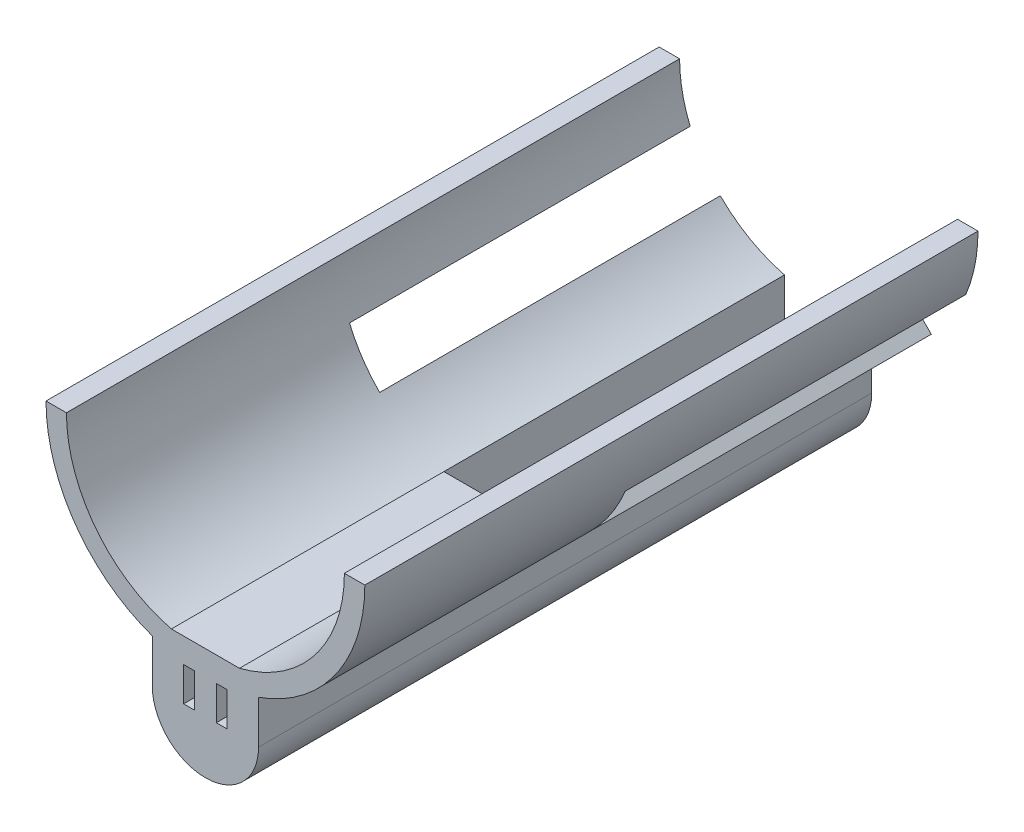
SolidWorks part; units mm, degrees
ref_plane "Front Plane" through (0, 0, 0) normal (0, 0, 1) x (1, 0, 0)
ref_plane "Top Plane" through (0, 0, 0) normal (0, 1, 0) x (1, 0, 0)
ref_plane "Right Plane" through (0, 0, 0) normal (1, 0, 0) x (0, 0, -1)
sketch "Sketch1" plane through (0, 0, 0) normal (0, 0, 1) x (1, 0, 0)
  line L0 (0, 20.4) -> (0, 23.4)
  line L1 (7.8067, 18.8471) -> (8.9548, 21.6188)
  line L2 (14.425, 14.425) -> (16.5463, 16.5463)
  line L3 (18.8471, 7.8067) -> (21.6188, 8.9548)
  line L4 (20.4, 0) -> (23.4, 0)
  line L5 (18.8471, -7.8067) -> (21.6188, -8.9548) [skipped]
  line L6 (14.425, -14.425) -> (16.5463, -16.5463) [skipped]
  line L7 (7.8067, -18.8471) -> (8.9548, -21.6188) [skipped]
  line L8 (0, -20.4) -> (0, -23.4) [skipped]
  line L9 (-7.8067, -18.8471) -> (-8.9548, -21.6188) [skipped]
  line L10 (-14.425, -14.425) -> (-16.5463, -16.5463) [skipped]
  line L11 (-18.8471, -7.8067) -> (-21.6188, -8.9548) [skipped]
  line L12 (-20.4, 0) -> (-23.4, 0)
  line L13 (-18.8471, 7.8067) -> (-21.6188, 8.9548)
  line L14 (-14.425, 14.425) -> (-16.5463, 16.5463)
  line L15 (-7.8067, 18.8471) -> (-8.9548, 21.6188)
  line L16 (-7.8, -28.4) -> (-7.8, -22.0617)
  line L18 (-5, -28.4) -> (-5, -19.7778)
  line L19 (5, -28.4) -> (5, -19.7778)
  line L21 (7.8, -28.4) -> (7.8, -22.0617)
  line L22 (-7.8, -36.2) -> (-7.8, -22.8596) construction
  line L23 (7.8, -36.2) -> (7.8, -22.8596) construction
  line L24 (-5, -33.4) -> (5, -33.4) construction
  line L25 (-5, -33.4) -> (-5, -22.8596) construction
  line L26 (5, -33.4) -> (5, -22.8596) construction
  line L27 (-7.8, -36.2) -> (7.8, -36.2) construction
  line L28 (7.8067, 18.8471) -> (8.9548, 21.6188) [skipped]
  line L29 (14.425, 14.425) -> (16.5463, 16.5463) [skipped]
  line L30 (18.8471, 7.8067) -> (21.6188, 8.9548) [skipped]
  line L31 (20.4, 0) -> (23.4, 0) [skipped]
  line L32 (18.8471, -7.8067) -> (21.6188, -8.9548)
  line L33 (14.425, -14.425) -> (16.5463, -16.5463)
  line L34 (7.8067, -18.8471) -> (8.9548, -21.6188)
  line L35 (0, -20.4) -> (0, -23.4)
  line L36 (-7.8067, -18.8471) -> (-8.9548, -21.6188)
  line L37 (-14.425, -14.425) -> (-16.5463, -16.5463)
  line L38 (-18.8471, -7.8067) -> (-21.6188, -8.9548)
  line L39 (-20.4, 0) -> (-23.4, 0) [skipped]
  line L40 (-18.8471, 7.8067) -> (-21.6188, 8.9548) [skipped]
  line L41 (-14.425, 14.425) -> (-16.5463, 16.5463) [skipped]
  line L42 (-7.8067, 18.8471) -> (-8.9548, 21.6188) [skipped]
  line L43 (-5, -19.7778) -> (5, -19.7778) construction
  line L44 (0, -19.7778) -> (0, -28.4) construction
  arc A0 (5, -19.7778) -> (-5, -19.7778) centre (0, 0) ccw
  arc A1 (7.8, -22.0617) -> (-7.8, -22.0617) centre (0, 0) ccw
  arc A2 (-5, -28.4) -> (5, -28.4) centre (0, -28.4) ccw
  arc A3 (-7.8, -28.4) -> (7.8, -28.4) centre (0, -28.4) ccw
  point P3 (7.8, -22.0617)
  point P6 (0, -23.4)
  point P7 (0, -20.4)
  point P33 (0, 0)
  point P40 (0, 0)
  point P45 (0, -33.4)
  point P54 (0, -28.4)
  point P55 (-5, -28.9793)
  point P56 (5, -28.9793)
  point P57 (-7.8, -22.0617)
  point P95 (0, 0)
  dimension "D1" = 40.8
  dimension "D2" = 46.8
  dimension "D6" = 10
  dimension "D4" = 2.8
  dimension "D5" = 16
  dimension "D8" = 10
  dimension "D9" = 8.6222
  dimension "D7" = 2.8
  dimension "D3" = 16
extrude "Boss-Extrude3" add sketch "Sketch1" along normal blind 40 contours L16 A3 L21 A1 L34 A0 L19 A2 L18 L36 | L34 A1 L33 A0 | L37 A1 L36 A0 | L12 A1 L38 A0 | L33 A1 L32 A0 | L32 A1 L4 A0 | L38 A1 L37 A0 region at (21.3748, -4.2517, 0) region at (-21.3748, -4.2517, 0) region at (18.1207, -12.1079, 0) region at (-18.1207, -12.1079, 0) region at (12.1079, -18.1207, 0) region at (-12.1079, -18.1207, 0) region at (8.1504, -20.3284, 0)
extrude "Boss-Extrude7" add sketch "Sketch1<12>" against normal blind 50 contours L34 A1 L33 A0 | L16 A3 L21 A1 L34 A0 L19 A2 L18 L36 | L12 A1 L38 A0 | L32 A1 L4 A0 | L37 A1 L36 A0 region at (21.3748, -4.2517, 0) region at (-21.3748, -4.2517, 0) region at (12.1079, -18.1207, 0) region at (-12.1079, -18.1207, 0) region at (8.1504, -20.3284, 0)
sketch "Sketch1<12>" plane through (0, 0, 0) normal (0, 0, 1) x (1, 0, 0) same geometry as "Sketch1"
sketch "Sketch3" plane through (0, 0, 40) normal (0, 0, 1) x (1, 0, 0)
  line L0 (-5, -19.7778) -> (5, -19.7778)
  line L1 (-5, -19.7778) -> (-5, -28.4)
  line L3 (5, -28.4) -> (5, -19.7778)
  line L9 (1.6, -23.4) -> (1.6, -28.4)
  line L13 (-1.6, -28.4) -> (-1.6, -23.4)
  line L14 (-1.6, -28.4) -> (-3.2, -28.4)
  line L15 (-1.6, -28.4) -> (-1.6, -23.4)
  line L16 (-1.6, -23.4) -> (-3.2, -23.4)
  line L17 (-3.2, -28.4) -> (-3.2, -23.4)
  line L18 (1.6, -28.4) -> (3.2, -28.4)
  line L19 (1.6, -28.4) -> (1.6, -23.4)
  line L20 (1.6, -23.4) -> (3.2, -23.4)
  line L21 (3.2, -28.4) -> (3.2, -23.4)
  arc A0 (-5, -28.4) -> (5, -28.4) centre (0, -28.4) ccw
  line M14 (5, -19.7778) -> (5, -28.4)
  arc M15 (5, -28.4) -> (-5, -28.4) centre (0, -28.4) cw
  line M16 (-5, -28.4) -> (-5, -19.7778)
  dimension "D1" = 10
  dimension "D5" = 1.6
  dimension "D6" = 1.6
extrude "Boss-Extrude8" add sketch "Sketch3" against normal blind 3 contours L0 L21 L18 L9 L20 L14 L17 L16 L13 M16 M15 M14 region at (0, -26.1315, 40)
sketch "Sketch5" plane through (0, 0, 37) normal (0, 0, -1) x (-1, 0, 0)
  line L0 (5, -28.4) -> (5, -19.7778) construction
  line L1 (-5, -19.7778) -> (5, -19.7778)
  line L2 (-5, -19.7778) -> (-5, -22.7778)
  line L3 (-5, -22.7778) -> (5, -22.7778)
  line L4 (5, -19.7778) -> (5, -22.7778)
  dimension "D1" = 10
  dimension "D2" = 3
extrude "Boss-Extrude9" add sketch "Sketch5" along normal blind 37
